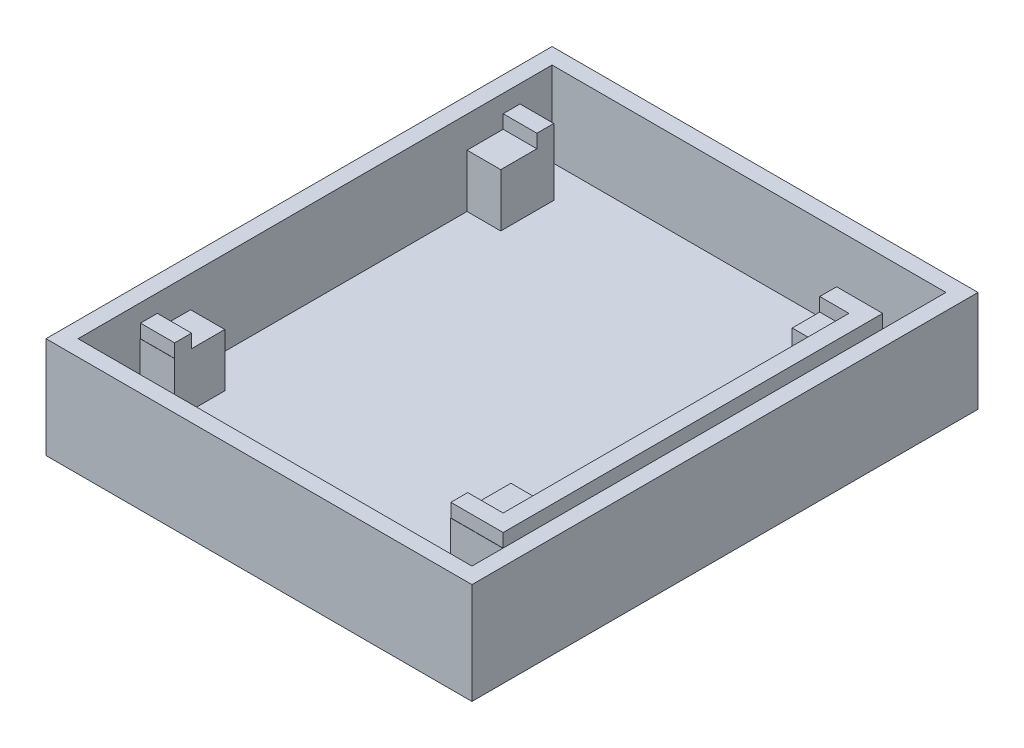
SolidWorks part; units mm, degrees
ref_plane "Piano frontale" through (0, 0, 0) normal (0, 0, 1) x (1, 0, 0)
ref_plane "Piano superiore" through (0, 0, 0) normal (0, 1, 0) x (1, 0, 0)
ref_plane "Piano destro" through (0, 0, 0) normal (1, 0, 0) x (0, 0, -1)
sketch "Schizzo1" plane through (0, 0, 0) normal (0, 1, 0) x (1, 0, 0)
  line L1 (0, 0) -> (50.5, 0)
  line L2 (0, 0) -> (0, 60)
  line L3 (0, 60) -> (50.5, 60)
  line L4 (50.5, 0) -> (50.5, 60)
  dimension "D1" = 60
  dimension "D2" = 50.5
extrude "Estrusione-Estrusione1" add sketch "Schizzo1" along normal blind 2
sketch "Schizzo2" plane through (0, 2, 0) normal (0, 1, 0) x (1, 0, 0)
  line L0 (0, 0) -> (50.5, 0) construction
  line L1 (0, 60) -> (1.9, 60)
  line L2 (0, 60) -> (0, 0)
  line L3 (0, 0) -> (1.9, 0)
  line L4 (1.9, 60) -> (1.9, 0)
  dimension "D1" = 1.9
extrude "Estrusione-Estrusione2" add sketch "Schizzo2" along normal blind 10
sketch "Schizzo3" plane through (0, 2, 0) normal (0, 1, 0) x (1, 0, 0)
  line L0 (50.5, 0) -> (50.5, 60) construction
  line L1 (1.9, 60) -> (50.5, 60)
  line L2 (1.9, 60) -> (1.9, 58.1)
  line L3 (1.9, 58.1) -> (50.5, 58.1)
  line L4 (50.5, 60) -> (50.5, 58.1)
  dimension "D1" = 1.9
extrude "Estrusione-Estrusione3" add sketch "Schizzo3" along normal blind 10
sketch "Schizzo4" plane through (0, 2, 0) normal (0, 1, 0) x (1, 0, 0)
  line L0 (1.9, 0) -> (50.5, 0) construction
  line L1 (50.5, 58.1) -> (48.6, 58.1)
  line L2 (50.5, 58.1) -> (50.5, 0)
  line L3 (50.5, 0) -> (48.6, 0)
  line L4 (48.6, 58.1) -> (48.6, 0)
  dimension "D1" = 1.9
extrude "Estrusione-Estrusione4" add sketch "Schizzo4" along normal blind 10
sketch "Schizzo5" plane through (0, 2, 0) normal (0, 1, 0) x (1, 0, 0)
  line L0 (48.6, 58.1) -> (48.6, 0) construction
  line L1 (1.9, 0) -> (48.6, 0)
  line L2 (1.9, 0) -> (1.9, 1.9)
  line L3 (1.9, 1.9) -> (48.6, 1.9)
  line L4 (48.6, 0) -> (48.6, 1.9)
  dimension "D1" = 1.9
extrude "Estrusione-Estrusione5" add sketch "Schizzo5" along normal blind 10
sketch "Schizzo8" plane through (0, 2, 0) normal (0, 1, 0) x (1, 0, 0)
  line L0 (1.9, 1.9) -> (1.9, 58.1) construction
  line L2 (1.9, 55.0174) -> (5.9, 55.0174)
  line L3 (1.9, 55.0174) -> (1.9, 48.0174)
  line L4 (1.9, 48.0174) -> (5.9, 48.0174)
  line L5 (5.9, 55.0174) -> (5.9, 48.0174)
  dimension "D1" = 4
  dimension "D2" = 7
extrude "Estrusione-Estrusione6" add sketch "Schizzo8" along normal blind 6.3
sketch "Schizzo13" plane through (0, 2, 0) normal (0, 1, 0) x (1, 0, 0)
  line L1 (39.4364, 55.0174) -> (45.2969, 55.0174)
  line L2 (39.4364, 55.0174) -> (39.4364, 49.0383)
  line L3 (39.4364, 49.0383) -> (45.2969, 49.0383)
  line L4 (45.2969, 55.0174) -> (45.2969, 49.0383)
  point P6 (45.2969, 39.3351)
  point P7 (0, 0)
extrude "Estrusione-Estrusione12" add sketch "Schizzo13" along normal blind 6.3
sketch "Schizzo14" plane through (0, 2, 0) normal (0, 1, 0) x (1, 0, 0)
  line L4 (45.2969, 16.4164) -> (38.6994, 16.4164)
  line L5 (45.2969, 16.4164) -> (45.2969, 9.2728)
  line L6 (45.2969, 9.2728) -> (38.6994, 9.2728)
  line L7 (38.6994, 16.4164) -> (38.6994, 9.2728)
extrude "Estrusione-Estrusione13" add sketch "Schizzo14" along normal blind 6.3
sketch "Schizzo15" plane through (0, 2, 0) normal (0, 1, 0) x (1, 0, 0)
  line L3 (1.9, 1.9) -> (1.9, 48.0174) construction
  line L5 (1.9, 9.2728) -> (5.9531, 9.2728)
  line L6 (1.9, 9.2728) -> (1.9, 15.2426)
  line L7 (1.9, 15.2426) -> (5.9531, 15.2426)
  line L8 (5.9531, 9.2728) -> (5.9531, 15.2426)
  point P11 (12.5694, 9.2728)
extrude "Estrusione-Estrusione14" add sketch "Schizzo15" along normal blind 6.3
sketch "Schizzo16" plane through (0, 8.3, 0) normal (0, 1, 0) x (1, 0, 0)
  line L0 (1.9, 55.0174) -> (1.9, 48.0174) construction
  line L1 (1.9, 52.3005) -> (5.9, 52.3005)
  line L2 (1.9, 52.3005) -> (1.9, 54.3005)
  line L3 (1.9, 54.3005) -> (5.9, 54.3005)
  line L4 (5.9, 52.3005) -> (5.9, 54.3005)
  line L5 (1.9, 52.3005) -> (18.7, 52.3005) construction
  line L6 (5.9, 48.0174) -> (5.9, 55.0174) construction
  dimension "D1" = 2
extrude "Estrusione-Estrusione15" add sketch "Schizzo16" along normal blind 1.6
sketch "Schizzo17" plane through (0, 8.3, 0) normal (0, 1, 0) x (1, 0, 0)
  line L0 (39.4364, 55.0174) -> (39.4364, 49.0383) construction
  line L1 (39.4364, 52.3005) -> (42.9, 52.3005)
  line L2 (39.4364, 52.3005) -> (39.4364, 54.3005)
  line L3 (39.4364, 54.3005) -> (42.9, 54.3005)
  line L4 (42.9, 52.3005) -> (42.9, 54.3005)
  line L5 (32.8, 52.3005) -> (42.9, 52.3005) construction
  dimension "D1" = 2
extrude "Estrusione-Estrusione16" add sketch "Schizzo17" along normal blind 1.6
sketch "Schizzo18" plane through (0, 8.3, 0) normal (0, 1, 0) x (1, 0, 0)
  line L0 (39.4364, 49.0383) -> (45.2969, 49.0383) construction
  line L1 (42.9, 49.0383) -> (44.9, 49.0383)
  line L2 (42.9, 49.0383) -> (42.9, 54.2995)
  line L3 (42.9, 54.2995) -> (44.9, 54.2995)
  line L4 (44.9, 49.0383) -> (44.9, 54.2995)
  line L5 (42.9, 52.3005) -> (42.9, 11.3005) construction
  dimension "D1" = 2
extrude "Estrusione-Estrusione17" add sketch "Schizzo18" along normal blind 1.6
sketch "Schizzo19" plane through (0, 8.3, 0) normal (0, 1, 0) x (1, 0, 0)
  line L1 (42.9, 52.3005) -> (42.9, 11.3005) construction
  line L2 (42.9, 16.4205) -> (44.9, 16.4205)
  line L3 (42.9, 16.4205) -> (42.9, 11.3005)
  line L4 (42.9, 11.3005) -> (44.9, 11.3005)
  line L5 (44.9, 16.4205) -> (44.9, 11.3005)
  dimension "D1" = 2
extrude "Estrusione-Estrusione18" add sketch "Schizzo19" along normal blind 1.6
sketch "Schizzo23" plane through (0, 8.3, 0) normal (0, 1, 0) x (1, 0, 0)
  line L0 (38.6994, 16.4164) -> (38.6994, 9.2728) construction
  line L1 (44.9, 11.3005) -> (38.6994, 11.3005)
  line L2 (44.9, 11.3005) -> (44.9, 9.3005)
  line L3 (44.9, 9.3005) -> (38.6994, 9.3005)
  line L4 (38.6994, 11.3005) -> (38.6994, 9.3005)
  dimension "D1" = 2
extrude "Estrusione-Estrusione19" add sketch "Schizzo23" along normal blind 1.6
sketch "Schizzo25" plane through (0, 8.3, 0) normal (0, 1, 0) x (1, 0, 0)
  line L0 (1.9, 15.2426) -> (1.9, 9.2728) construction
  line L1 (1.9, 11.2993) -> (5.9531, 11.2993)
  line L2 (1.9, 11.2993) -> (1.9, 9.2993)
  line L3 (1.9, 9.2993) -> (5.9531, 9.2993)
  line L4 (5.9531, 11.2993) -> (5.9531, 9.2993)
  line L5 (5.9531, 9.2728) -> (5.9531, 15.2426) construction
  dimension "D1" = 2
extrude "Estrusione-Estrusione20" add sketch "Schizzo25" along normal blind 1.6
sketch "Schizzo26" plane through (0, 8.3, 0) normal (0, 1, 0) x (1, 0, 0)
  line L0 (38.6994, 9.2728) -> (45.2969, 9.2728) construction
  line L1 (44.9, 16.4164) -> (45.2969, 16.4164)
  line L2 (44.9, 16.4164) -> (44.9, 9.2728)
  line L3 (44.9, 9.2728) -> (45.2969, 9.2728)
  line L4 (45.2969, 16.4164) -> (45.2969, 9.2728)
  line L5 (38.6994, 9.2728) -> (45.2969, 9.2728) construction
extrude "Taglio-Estrusione1" cut sketch "Schizzo26" against normal blind 6.3
sketch "Schizzo27" plane through (0, 8.3, 0) normal (0, 1, 0) x (1, 0, 0)
  line L1 (45.2969, 55.0174) -> (44.9, 55.0174)
  line L2 (45.2969, 55.0174) -> (45.2969, 49.0383)
  line L3 (45.2969, 49.0383) -> (44.9, 49.0383)
  line L4 (44.9, 55.0174) -> (44.9, 49.0383)
extrude "Taglio-Estrusione2" cut sketch "Schizzo27" against normal blind 6.3
sketch "Schizzo28" plane through (0, 8.3, 0) normal (0, 1, 0) x (1, 0, 0)
  line L1 (39.4364, 55.0174) -> (44.9, 55.0174)
  line L2 (39.4364, 55.0174) -> (39.4364, 54.2995)
  line L3 (39.4364, 54.2995) -> (44.9, 54.2995)
  line L4 (44.9, 55.0174) -> (44.9, 54.2995)
extrude "Taglio-Estrusione3" cut sketch "Schizzo28" against normal blind 6.3
sketch "Schizzo29" plane through (0, 8.3, 0) normal (0, 1, 0) x (1, 0, 0)
  line L1 (1.9, 55.0174) -> (5.9, 55.0174)
  line L2 (1.9, 55.0174) -> (1.9, 54.3005)
  line L3 (1.9, 54.3005) -> (5.9, 54.3005)
  line L4 (5.9, 55.0174) -> (5.9, 54.3005)
extrude "Taglio-Estrusione4" cut sketch "Schizzo29" against normal blind 6.3
sketch "Schizzo30" plane through (0, 0, -49.0383) normal (0, 0, 1) x (1, 0, 0)
  line L1 (44.9, 9.9) -> (42.9, 9.9)
  line L2 (44.9, 9.9) -> (44.9, 8.3)
  line L3 (44.9, 8.3) -> (42.9, 8.3)
  line L4 (42.9, 9.9) -> (42.9, 8.3)
extrude "Estrusione-Estrusione21" add sketch "Schizzo30" along normal blind 33.3
